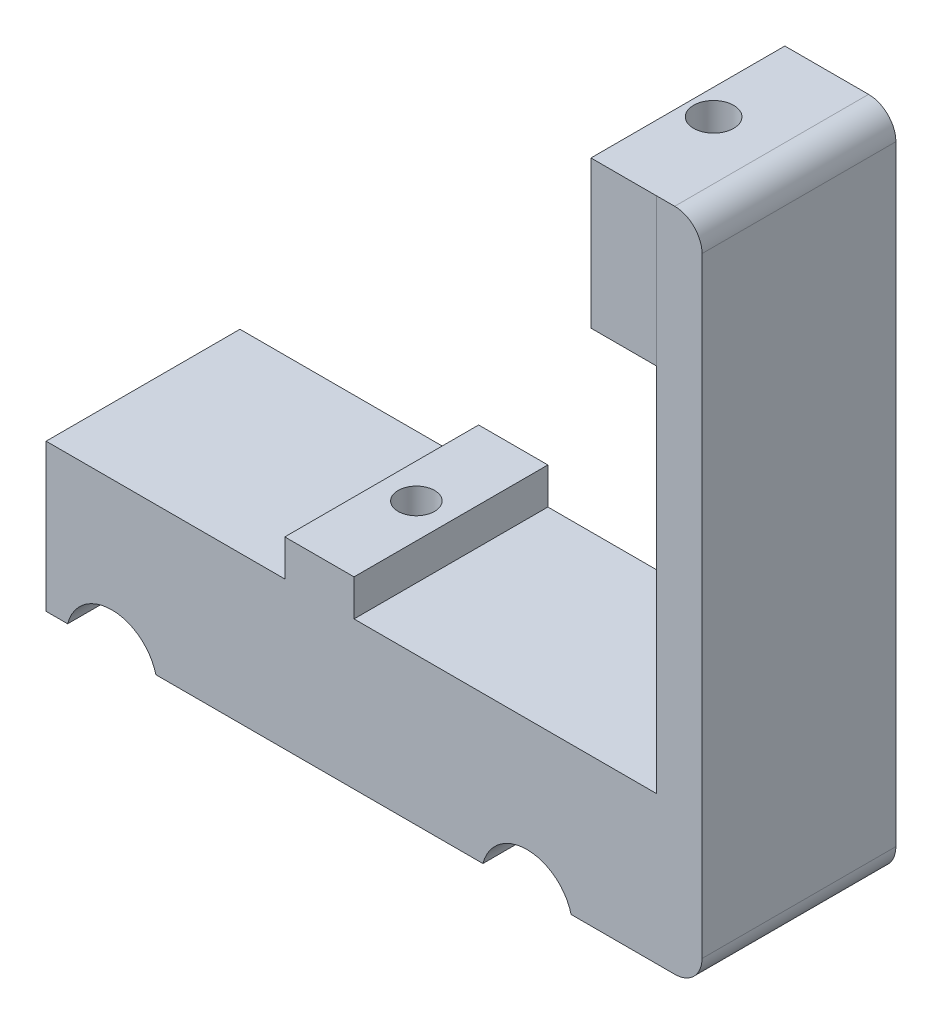
SolidWorks part; units mm, degrees
ref_plane "Front Plane" through (0, 0, 0) normal (0, 0, 1) x (1, 0, 0)
ref_plane "Top Plane" through (0, 0, 0) normal (0, 1, 0) x (1, 0, 0)
ref_plane "Right Plane" through (0, 0, 0) normal (1, 0, 0) x (0, 0, -1)
sketch "Sketch2" plane through (0, 0, 0) normal (0, 0, 1) x (1, 0, 0)
  line L0 (10.1, 0) -> (-10.1, 0)
  line L1 (-10.1, 0) -> (-10.1, 1.7099)
  line L2 (-10.1, 1.7099) -> (-6.2548, 7)
  line L3 (-6.2548, 7) -> (6.2548, 7)
  line L4 (0, 7) -> (0, 0)
  line L5 (0, 0) -> (0, 9.2516) construction
  line L6 (10.1, 1.7099) -> (6.2548, 7)
  line L7 (10.1, 0) -> (10.1, 1.7099)
  dimension "D1" = 20.2
  dimension "D2" = 7
extrude "Boss-Extrude1" add sketch "Sketch2" along normal blind 10.8 contours L4 L3 L2 L1 L0 | L0 L7 L6 L3 L4 region at (4.4168, 3.2082, 0) region at (-4.4168, 3.2082, 0)
sketch "Sketch4" plane through (0, 0, 0) normal (0, 0, 1) x (1, 0, 0)
  line L0 (-3.8, 0) -> (-3.8, -4.8)
  line L1 (10.1, 0) -> (-10.1, 0) construction
  line L2 (-3.8, -4.8) -> (-30, -4.8)
  line L3 (-30, -4.8) -> (-30, -29.8)
  line L4 (-30, -29.8) -> (30, -29.8)
  line L5 (0, 0) -> (0, -29.8) construction
  line L6 (0, -29.8) -> (0, 0)
  line L7 (3.8, 0) -> (-3.8, 0)
  line L8 (0, 0) -> (0, -30.5381) construction
  line L9 (30, -4.8) -> (30, -29.8)
  line L10 (3.8, -4.8) -> (30, -4.8)
  line L11 (3.8, 0) -> (3.8, -4.8)
  line L13 (-30, -20.98) -> (30, -20.98)
  line L14 (-30, -20.98) -> (-30, -23.48)
  line L15 (-30, -23.48) -> (30, -23.48)
  line L16 (30, -20.98) -> (30, -23.48)
  dimension "D1" = 4.8
  dimension "D2" = 3.8
  dimension "D3" = 25
  dimension "D4" = 60
  dimension "D6" = 8.82
extrude "Boss-Extrude2" add sketch "Sketch4" along normal mid plane 21.28 contours L6 L7 L0 L2 L3 L4 | L11 L7 L6 L4 L9 L10 region at (-14.5256, -12.5101, 0) region at (14.5256, -12.5101, 0)
sketch "Sketch5" plane through (0, 0, 0) normal (0, 0, 1) x (1, 0, 0)
  line L0 (-29.791, -22.2274) -> (26.9734, -22.2274) construction
  line L3 (0, -20.98) -> (0, 7) construction
  line L5 (-6.2548, 7) -> (6.2548, 7) construction
  line L20 (-30, -20.98) -> (30, -20.98) construction
  circle A0 centre (-22.791, -22.2274) radius 5
  circle A1 centre (22.791, -22.2274) radius 5
  dimension "D1" = 7
extrude "Cut-Extrude1" cut sketch "Sketch5" along normal through all both and the other way through all
fillet "Fillet1" radius 1 6 edges at (-10.1, 0, 5.4) (-10.1, 1.7099, 5.4) (-6.2548, 7, 5.4) (6.2548, 7, 5.4) (10.1, 0, 5.4) (10.1, 1.7099, 5.4)
sketch "Sketch6" plane through (30, 0, 0) normal (1, 0, 0) x (0, 0, -1)
  line L0 (-10.64, -20.98) -> (10.64, -20.98) construction
  line L1 (-10.64, -4.8) -> (10.64, -4.8)
  line L2 (-10.64, -4.8) -> (-10.64, -20.98)
  line L3 (-10.64, -20.98) -> (10.64, -20.98)
  line L4 (10.64, -4.8) -> (10.64, -20.98)
extrude "Boss-Extrude3" add sketch "Sketch6" along normal blind 12
sketch "Sketch7" plane through (0, -4.8, 0) normal (0, 1, 0) x (1, 0, 0)
  line L0 (3.8, -10.64) -> (42, -10.64) construction
  line L1 (42, 10.6413) -> (37, 10.6413)
  line L2 (42, 10.6413) -> (42, -10.64)
  line L3 (42, -10.64) -> (37, -10.64)
  line L4 (37, 10.6413) -> (37, -10.64)
  dimension "D1" = 5
extrude "Boss-Extrude4" add sketch "Sketch7" along normal blind 56.83
sketch "Sketch8" plane through (37, 0, 0) normal (-1, 0, 0) x (0, 0, 1)
  line L0 (-10.6413, 52.03) -> (-10.6413, -4.8) construction
  line L1 (10.643, 52.03) -> (-10.6413, 52.03)
  line L2 (10.643, 52.03) -> (10.643, 35.85)
  line L3 (10.643, 35.85) -> (-10.6413, 35.85)
  line L4 (-10.6413, 52.03) -> (-10.6413, 35.85)
  dimension "D1" = 16.18
extrude "Boss-Extrude5" add sketch "Sketch8" along normal blind 7.19
fillet "Fillet3" radius 3 2 edges at (42, 52.03, -0.0007) (42, -20.98, 0)
sketch "Sketch9" plane through (0, -20.98, 0) normal (0, -1, 0) x (1, 0, 0)
  line L0 (27.6329, 0) -> (27.6329, 10.8) construction
  line L2 (27.6329, 10.64) -> (39, 10.64) construction
  circle A0 centre (32.6329, 0) radius 2.2
  dimension "D1" = 5
  dimension "D2" = 10.64
extrude "Cut-Extrude2" cut sketch "Sketch9" against normal through all
sketch "Sketch10" plane through (0, -20.98, 0) normal (0, -1, 0) x (1, 0, 0)
  line L2 (-17.9491, 0) -> (-17.9491, 10.8) construction
  line L3 (-17.9491, 10.64) -> (17.9491, 10.64) construction
  circle A0 centre (0.0009, 0) radius 2
  dimension "D1" = 10.64
  dimension "D2" = 17.95
extrude "Cut-Extrude3" cut sketch "Sketch10" against normal through all
sketch "Sketch11" plane through (0, 0, 10.8) normal (0, 0, 1) x (1, 0, 0)
  line L0 (9.1, 0) -> (-9.1, 0) construction
  line L1 (-12.6098, 8.9215) -> (12.3675, 8.9215)
  line L2 (-12.6098, 8.9215) -> (-12.6098, -0.8)
  line L3 (-12.6098, -0.8) -> (12.3675, -0.8)
  line L4 (12.3675, 8.9215) -> (12.3675, -0.8)
  dimension "D1" = 0.8
extrude "Cut-Extrude4" cut sketch "Sketch11" against normal through all
